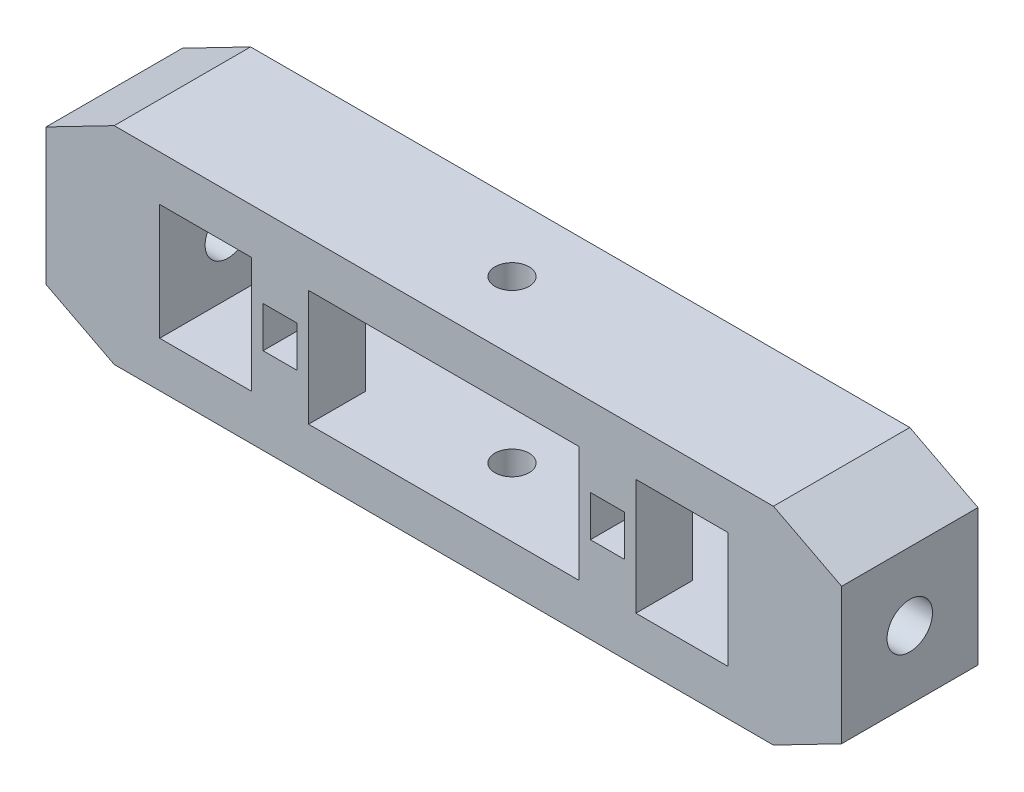
SolidWorks part; units mm, degrees
note: The reader was unsure of these and kept them because the rebuilt part matched: shared geometry of "Sketch2<3>", "Sketch6<3>".
ref_plane "Front Plane" through (0, 0, 0) normal (0, 0, 1) x (1, 0, 0)
ref_plane "Top Plane" through (0, 0, 0) normal (0, 1, 0) x (1, 0, 0)
ref_plane "Right Plane" through (0, 0, 0) normal (1, 0, 0) x (0, 0, -1)
sketch "Sketch1" plane through (0, 0, 0) normal (0, 1, 0) x (1, 0, 0)
  line L1 (-12.5, -3) -> (12.5, -3)
  line L2 (-12.5, -3) -> (-12.5, 3)
  line L3 (-12.5, 3) -> (12.5, 3)
  line L4 (12.5, -3) -> (12.5, 3)
  line L5 (0, 3) -> (0, -3) construction
  line L6 (-12.5, 0) -> (12.5, 0) construction
  circle A0 centre (0, 0) radius 0.75
  point P0 (0, 0)
  dimension "D3" = 1.5
  dimension "D1" = 25
  dimension "D2" = 6
extrude "BaseFrame" add sketch "Sketch1" along normal blind 2
ref_plane "Plane1" through (0, 7.1, 0) normal (0, 1, 0) x (1, 0, 0)
sketch "Sketch2" plane through (0, 7.1, 0) normal (0, 1, 0) x (1, 0, 0)
  line L0 (0, 0) -> (0, 1.6813) construction
  line L1 (-12.5, 3) -> (-14.5, 3)
  line L2 (-14.5, 3) -> (-14.5, -3)
  line L3 (-14.5, -3) -> (-12.5, -3)
  line L4 (12.5, -3) -> (12.5, 3)
  line L5 (12.5, 3) -> (-12.5, 3)
  line L6 (-12.5, 3) -> (-12.5, -3)
  line L7 (-12.5, -3) -> (12.5, -3)
  line L8 (12.5, -3) -> (12.5, 3)
  line L9 (12.5, 3) -> (-12.5, 3)
  line L10 (-12.5, 3) -> (-12.5, -3)
  line L11 (-12.5, -3) -> (12.5, -3)
  line L12 (14.5, -3) -> (12.5, -3)
  line L13 (12.5, 3) -> (14.5, 3)
  line L14 (14.5, 3) -> (14.5, -3)
  circle A0 centre (0, 0) radius 0.75 construction
  circle A1 centre (0, 0) radius 0.75
  dimension "D2" = 2
  dimension "D1" = 0
extrude "Boss-Extrude2" add sketch "Sketch2" along normal blind 2 separate body
extrude "Boss-Extrude3" add sketch "Sketch2<3>" against normal up to surface (7.1 mm away) contours L10 L1 L2 L3 | L14 L13 L8 L12 up to face at (0, 0, 0)
sketch "Sketch2<3>" plane through (0, 7.1, 0) normal (0, 1, 0) x (1, 0, 0) same geometry as "Sketch2"
sketch "Sketch3" plane through (0, 0, -3) normal (0, 0, -1) x (-1, 0, 0)
  line L0 (0, 9.1) -> (0, 0) construction
  line L1 (14.5, 9.1) -> (17.5, 7.55)
  line L2 (17.5, 7.55) -> (17.5, 1.55)
  line L3 (17.5, 4.55) -> (14.5, 4.55) construction
  line L4 (-14.5, 9.1) -> (-14.5, 0)
  line L5 (-14.5, 0) -> (14.5, 0)
  line L6 (14.5, 0) -> (14.5, 9.1)
  line L7 (14.5, 9.1) -> (-14.5, 9.1)
  line L8 (-14.5, 9.1) -> (-14.5, 0)
  line L9 (-14.5, 0) -> (14.5, 0)
  line L10 (14.5, 0) -> (14.5, 9.1)
  line L11 (14.5, 9.1) -> (-14.5, 9.1)
  line L12 (14.5, 0) -> (17.5, 1.55)
  line L13 (-14.5, 0) -> (-17.5, 1.55)
  line L14 (-17.5, 7.55) -> (-17.5, 1.55)
  line L15 (-14.5, 9.1) -> (-17.5, 7.55)
  line M10 (-14.5, 9.1) -> (-14.5, 0)
  line M12 (14.5, 0) -> (14.5, 9.1)
  dimension "D2" = 3
  dimension "D3" = 3
  dimension "D1" = 0
extrude "Boss-Extrude4" add sketch "Sketch3" against normal up to surface (6 mm away) contours L15 L14 L13 M10 | L12 L2 L1 M12 up to face at (0, 4.55, 3)
sketch "Sketch4" plane through (-17.5, 0, 0) normal (-1, 0, 0) x (0, 0, 1)
  line L0 (-3, 4.55) -> (3, 4.55) construction
  line L4 (-3, 1.55) -> (3, 1.55)
  line L5 (3, 1.55) -> (3, 7.55)
  line L6 (3, 7.55) -> (-3, 7.55)
  line L7 (-3, 7.55) -> (-3, 1.55)
  line L8 (-3, 1.55) -> (3, 1.55) construction
  line L9 (3, 1.55) -> (3, 7.55) construction
  line L10 (3, 7.55) -> (-3, 7.55) construction
  line L11 (-3, 7.55) -> (-3, 1.55) construction
  circle A0 centre (0, 4.55) radius 1
  dimension "D2" = 2
  dimension "D1" = 0
extrude "ShaftHole" cut sketch "Sketch4" against normal through all
sketch "Sketch5" plane through (0, 9.1, 0) normal (0, 1, 0) x (1, 0, 0)
  line L0 (-14.5, -3) -> (14.5, -3) construction
  line L1 (-14.5, -3) -> (14.5, -3) construction
  line L2 (7.2, -3) -> (7.2, -1.75) construction
  line L4 (5.95, -3) -> (8.45, -3)
  line L5 (5.95, -3) -> (5.95, -0.5)
  line L6 (5.95, -0.5) -> (8.45, -0.5)
  line L7 (8.45, -3) -> (8.45, -0.5)
  line L8 (7.2, -0.5) -> (7.2, -3) construction
  line L9 (5.95, -1.75) -> (8.45, -1.75) construction
  arc A0 (1.1966, 5.573) -> (5.6961, 0.2107) centre (0, 0) ccw construction
  arc A1 (1.1966, 5.573) -> (5.6961, 0.2107) centre (0, 0) ccw construction
  arc A2 (1.1966, 5.573) -> (5.6961, 0.2107) centre (0, 0) cw construction
  dimension "D1" = 2.5
  dimension "D2" = 2.5
  dimension "D3" = 1.25
  dimension "D4" = 7.2
extrude "SlotBlock" add sketch "Sketch5" along normal up to surface (5.1 mm away) from surface
sketch "Sketch6" plane through (0, 0, 3) normal (0, 0, 1) x (1, 0, 0)
  line L0 (5.95, 2) -> (5.95, 7.1) construction
  line L1 (8.45, 2) -> (8.45, 7.1) construction
  line L2 (5.95, 2) -> (5.95, 7.1) construction
  line L3 (8.45, 2) -> (8.45, 7.1) construction
  line L4 (5.95, 4.55) -> (8.45, 4.55) construction
  line L6 (6.45, 3.8) -> (7.95, 3.8)
  line L7 (6.45, 3.8) -> (6.45, 5.3)
  line L8 (6.45, 5.3) -> (7.95, 5.3)
  line L9 (7.95, 3.8) -> (7.95, 5.3)
  line L10 (7.2, 5.3) -> (7.2, 3.8) construction
  line L11 (6.45, 4.55) -> (7.95, 4.55) construction
  line L12 (6.75, 4.1) -> (7.65, 4.1)
  line L13 (6.75, 4.1) -> (6.75, 5)
  line L14 (6.75, 5) -> (7.65, 5)
  line L15 (7.65, 4.1) -> (7.65, 5)
  line L16 (7.2, 5) -> (7.2, 4.1) construction
  line L17 (6.75, 4.55) -> (7.65, 4.55) construction
  point P6 (7.2, 4.55)
  point P10 (7.2, 4.55)
  dimension "D1" = 1.5
  dimension "D2" = 1.5
  dimension "D3" = 0.9
  dimension "D4" = 0.9
extrude "ClipEntrance" cut sketch "Sketch6" against normal blind 2 contours L12 L15 L14 L13 | L6 L9 L8 L7 L15 L12 L13 L14
extrude "CableExit" cut sketch "Sketch6<3>" against normal through all contours L12 L15 L14 L13
sketch "Sketch6<3>" plane through (0, 0, 3) normal (0, 0, 1) x (1, 0, 0) same geometry as "Sketch6"
sketch "Sketch7" plane through (0, 5.3, 0) normal (0, -1, 0) x (1, 0, 0)
  line L0 (6.45, 2.5) -> (7.95, 2.5)
  line L4 (7.95, 3) -> (6.45, 3)
  line L5 (6.45, 3) -> (6.45, 1)
  line L6 (6.45, 1) -> (7.95, 1)
  line L7 (7.95, 1) -> (7.95, 3)
  line L8 (7.95, 3) -> (6.45, 3)
  line L9 (6.45, 3) -> (6.45, 1)
  line L10 (6.45, 1) -> (7.95, 1)
  line L11 (7.95, 1) -> (7.95, 3)
  line M7 (6.45, 3) -> (6.45, 1)
  line M8 (6.45, 1) -> (7.95, 1)
  line M9 (7.95, 1) -> (7.95, 3)
  dimension "D2" = 0.5
  dimension "D1" = 0
extrude "ClipLockSlot" cut sketch "Sketch7" against normal blind 0.6 contours L0 M7 M8 M9
sketch "Sketch8" plane through (0, 0, 3) normal (0, 0, 1) x (1, 0, 0)
  line L0 (6.45, 5.3) -> (7.95, 5.3) construction
  line L1 (6.45, 5.3) -> (7.95, 5.3)
  line L2 (6.45, 5.3) -> (6.45, 5.6)
  line L3 (6.45, 5.6) -> (7.95, 5.6)
  line L4 (7.95, 5.6) -> (7.95, 5.3)
  dimension "D1" = 0.3
extrude "ClipLockClearanceCut" cut sketch "Sketch8" against normal up to surface (0.5 mm away) up to face at (7.2, 5.6, 2.5)
mirror "Mirror1" about plane through (0, 0, 0) normal (1, 0, 0) of "ClipLockClearanceCut", "ClipLockSlot", "CableExit", "ClipEntrance", "SlotBlock"
equation "\"Bolt1_D\"=2mm"
equation "\"Bolt1_HeadD\"=3.2mm"
equation "\"Bolt1_NutD\"=3.9mm"
equation "\"Bolt2_D\"=1.6mm"
equation "\"Bolt2_HeadD\"=2.9mm"
equation "\"Bolt2_HeadThickness\"=1mm"
equation "\"Bolt2_NutD\"=2.5mm"
equation "\"Bolt2_NutThickness\"=1.4mm"
equation "\"Screw1_D\"=1.2mm"
equation "\"Screw1_HeadD\"=2mm"
equation "\"Tube1_InnerD\"=0.8mm"
equation "\"Tube1_OuterD\"=1.2mm"
equation "\"Tube2_InnerD\"=0.3mm"
equation "\"Tube2_OuterD\"=0.8mm"
equation "\"TubeClipW\"=1.5mm"
equation "\"TubeClipH_Tube1\"=1.5mm"
equation "\"TubeClipH_Tube2\"=1.1mm"
equation "\"TubeClipLock_SideL\"=1.5mm"
equation "\"TubeClipLock_W\"=0.7mm"
equation "\"Pulley_GrooveDepth\"=0.7mm"
equation "\"Cable_D\"=0.3mm"
equation "\"BallBearing1_InnerD\"=2mm"
equation "\"BallBearing1_OuterD\"=4mm"
equation "\"BallBearing1_Thickness\"=2mm"
equation "\"BallBearing2_InnerD\"=1.5mm"
equation "\"BallBearing2_OuterD\"=4mm"
equation "\"BallBearing2_Thickness\"=1.2mm"
equation "\"BallBearing3_InnerD\"=1mm"
equation "\"BallBearing3_OuterD\"=3mm"
equation "\"BallBearing3_Thickness\"=1mm"
equation "\"HumerusL\"=37.2mm"
equation "\"HumerusElbowSidePulleyD\"=10mm"
equation "\"RadiusL\"=68.1mm"
equation "\"ElbowExtendedAngle\"=140deg"
equation "\"ElbowFlexedAngle\"=38deg"
equation "\"Digit5ExtendedAngle\"=80deg"
equation "\"Digit5FlexedAngle\"=24deg"
equation "\"Digit4ExtendedAngle\"=108deg"
equation "\"Digit4FlexedAngle\"=34deg"
equation "\"Digit3ExtendedAngle\"=145deg"
equation "\"Digit3FlexedAngle\"=44deg"
equation "\"KST_Servo_ShaftBolt_D\"=2.5mm"
equation "\"KST_Servo_ShaftBolt_HeadD\"=5.2mm"
equation "\"XL330_M077_T_HornScrew_D\"=1.9mm"
equation "\"XL330_M077_T_HornScrew_HeadD\"=3.3mm"
equation "\"D3@Sketch1\"=\"BallBearing2_InnerD\""
equation "\"D1@Sketch6\"=\"TubeClipW\""
equation "\"D2@Sketch6\"=\"TubeClipH_Tube1\""
